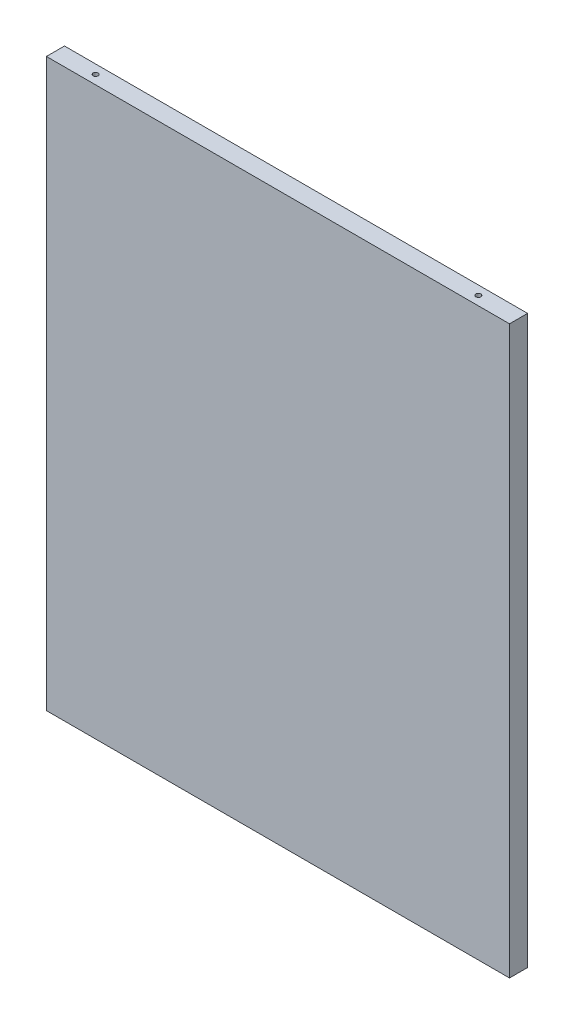
SolidWorks part; units mm, degrees
material "ДСП"
ref_plane "Спереди" through (0, 0, 0) normal (0, 0, 1) x (1, 0, 0)
ref_plane "Сверху" through (0, 0, 0) normal (0, 1, 0) x (1, 0, 0)
ref_plane "Справа" through (0, 0, 0) normal (1, 0, 0) x (0, 0, -1)
sketch "Эскиз1" plane through (0, 0, 0) normal (0, 0, 1) x (1, 0, 0)
  line L1 (0, 0) -> (461, 0)
  line L2 (0, 0) -> (0, 564)
  line L3 (0, 564) -> (461, 564)
  line L4 (461, 0) -> (461, 564)
  dimension "D1" = 564
  dimension "D2" = 461
extrude "Придание толщины" add sketch "Эскиз1" along normal blind 18
sketch "Эскиз3" plane through (0, 0, 18) normal (0, 0, 1) x (1, 0, 0)
  line L0 (0, 564) -> (0, 0) construction
  line L1 (0, 0) -> (461, 0) construction
  circle A0 centre (0, 0) radius 4
  dimension "D1" = 8
  dimension "D2" = 0
  dimension "D3" = 0
extrude "Отверстие 1" [suppressed] cut sketch "Эскиз3" against normal blind 16
sketch "Эскиз4" plane through (0, 0, 18) normal (0, 0, 1) x (1, 0, 0)
  line L0 (0, 564) -> (0, 0) construction
  line L1 (0, 0) -> (461, 0) construction
  circle A0 centre (0, 0) radius 4
  dimension "D2" = 0
  dimension "D3" = 8
extrude "Отверстие 2" [suppressed] cut sketch "Эскиз4" against normal blind 16
sketch "Эскиз5" plane through (0, 0, 18) normal (0, 0, 1) x (1, 0, 0)
  line L0 (0, 564) -> (0, 0) construction
  line L1 (0, 0) -> (461, 0) construction
  circle A0 centre (0, 0) radius 4
  dimension "D1" = 8
extrude "Отверстие 3" [suppressed] cut sketch "Эскиз5" against normal blind 16
sketch "Эскиз6" plane through (0, 0, 18) normal (0, 0, 1) x (1, 0, 0)
  line L0 (0, 564) -> (0, 0) construction
  line L1 (0, 0) -> (461, 0) construction
  circle A0 centre (0, 0) radius 4
  dimension "D1" = 8
extrude "Отверстие 4" [suppressed] cut sketch "Эскиз6" against normal blind 16
sketch "Эскиз7" plane through (0, 0, 18) normal (0, 0, 1) x (1, 0, 0)
  line L0 (0, 564) -> (0, 0) construction
  line L1 (0, 0) -> (461, 0) construction
  circle A0 centre (0, 0) radius 4
  dimension "D1" = 8
extrude "Отверстие 5" [suppressed] cut sketch "Эскиз7" against normal blind 16
sketch "Эскиз8" plane through (0, 0, 18) normal (0, 0, 1) x (1, 0, 0)
  line L0 (0, 564) -> (0, 0) construction
  line L1 (0, 0) -> (461, 0) construction
  circle A0 centre (0, 0) radius 4
  dimension "D1" = 8
extrude "Отверстие 6" [suppressed] cut sketch "Эскиз8" against normal blind 16
sketch "Эскиз9" plane through (0, 0, 18) normal (0, 0, 1) x (1, 0, 0)
  line L0 (0, 564) -> (0, 0) construction
  line L1 (0, 0) -> (461, 0) construction
  circle A0 centre (0, 0) radius 4
  dimension "D1" = 8
extrude "Отверстие 7" [suppressed] cut sketch "Эскиз9" against normal blind 16
sketch "Эскиз10" plane through (0, 0, 18) normal (0, 0, 1) x (1, 0, 0)
  line L0 (0, 564) -> (0, 0) construction
  line L1 (0, 0) -> (461, 0) construction
  circle A0 centre (0, 0) radius 4
  dimension "D1" = 8
extrude "Отверстие 8" [suppressed] cut sketch "Эскиз10" against normal blind 16
sketch "Эскиз27" plane through (0, 0, 18) normal (0, 0, 1) x (1, 0, 0)
  line L2 (0, 564) -> (0, 0) construction
  line L3 (0, 0) -> (461, 0) construction
  circle A0 centre (0, 0) radius 4
  dimension "D1" = 8
  dimension "D3" = 0
extrude "Отверстие 9" [suppressed] cut sketch "Эскиз27" against normal blind 10
sketch "Эскиз29" plane through (0, 0, 18) normal (0, 0, 1) x (1, 0, 0)
  line L2 (0, 564) -> (0, 0) construction
  line L3 (0, 0) -> (461, 0) construction
  circle A0 centre (0, 0) radius 4
  dimension "D1" = 8
extrude "Отверстие 10" [suppressed] cut sketch "Эскиз29" against normal blind 10
sketch "Эскиз30" plane through (0, 0, 18) normal (0, 0, 1) x (1, 0, 0)
  line L1 (0, 0) -> (461, 0) construction
  line L3 (0, 564) -> (0, 0) construction
  circle A0 centre (0, 0) radius 4
  dimension "D1" = 8
extrude "Отверстие 11" [suppressed] cut sketch "Эскиз30" against normal blind 10
sketch "Эскиз31" plane through (0, 0, 18) normal (0, 0, 1) x (1, 0, 0)
  line L2 (0, 0) -> (461, 0) construction
  line L3 (0, 564) -> (0, 0) construction
  circle A0 centre (0, 0) radius 4
  dimension "D1" = 8
extrude "Отверстие 12" [suppressed] cut sketch "Эскиз31" against normal blind 10
sketch "Эскиз11" plane through (0, 564, 0) normal (0, 1, 0) x (1, 0, 0)
  line L0 (0, -18) -> (0, 0) construction
  line L1 (461, -18) -> (0, -18) construction
  circle A0 centre (40, -9) radius 2.5
  dimension "D1" = 5
  dimension "D2" = 40
  dimension "D3" = 9
extrude "Отверстие А1" cut sketch "Эскиз11" against normal blind 37
sketch "Эскиз12" plane through (0, 564, 0) normal (0, 1, 0) x (1, 0, 0)
  line L1 (0, -18) -> (0, 0) construction
  line L2 (461, -18) -> (0, -18) construction
  circle A0 centre (421, -9) radius 2.5
  dimension "D1" = 5
  dimension "D3" = 9
  dimension "D2" = 421
extrude "Отверстие А2" cut sketch "Эскиз12" against normal blind 37
sketch "Эскиз13" plane through (0, 564, 0) normal (0, 1, 0) x (1, 0, 0)
  line L1 (0, -18) -> (0, 0) construction
  line L2 (461, -18) -> (0, -18) construction
  circle A0 centre (0, -18) radius 4
  dimension "D1" = 8
  dimension "D3" = 0
extrude "Отверстие А3" [suppressed] cut sketch "Эскиз13" against normal blind 20
sketch "Эскиз14" plane through (0, 564, 0) normal (0, 1, 0) x (1, 0, 0)
  line L0 (0, -18) -> (0, 0) construction
  line L1 (461, -18) -> (0, -18) construction
  circle A0 centre (0, -10) radius 4
  dimension "D1" = 8
  dimension "D3" = 8
extrude "Отверстие А4" [suppressed] cut sketch "Эскиз14" against normal blind 20
sketch "Эскиз15" plane through (461, 0, 0) normal (1, 0, 0) x (0, 0, -1)
  line L0 (-18, 564) -> (0, 564) construction
  line L1 (-18, 0) -> (-18, 564) construction
  circle A0 centre (-18, 564) radius 2.5
  dimension "D2" = 0
  dimension "D3" = 0
  dimension "D1" = 5
extrude "Отверстие В1" [suppressed] cut sketch "Эскиз15" against normal blind 37
sketch "Эскиз16" plane through (461, 0, 0) normal (1, 0, 0) x (0, 0, -1)
  line L0 (-18, 564) -> (0, 564) construction
  line L1 (-18, 0) -> (-18, 564) construction
  circle A0 centre (-18, 564) radius 2.5
  dimension "D1" = 5
extrude "Отверстие В2" [suppressed] cut sketch "Эскиз16" against normal blind 37
sketch "Эскиз17" plane through (461, 0, 0) normal (1, 0, 0) x (0, 0, -1)
  line L1 (-18, 564) -> (0, 564) construction
  line L2 (-18, 0) -> (-18, 564) construction
  circle A0 centre (-18, 564) radius 4
  dimension "D1" = 8
  dimension "D2" = 0
  dimension "D3" = 0
extrude "Отверстие В3" [suppressed] cut sketch "Эскиз17" against normal blind 20
sketch "Эскиз18" plane through (461, 0, 0) normal (1, 0, 0) x (0, 0, -1)
  line L0 (-18, 564) -> (0, 564) construction
  line L1 (-18, 0) -> (-18, 564) construction
  circle A0 centre (-18, 564) radius 4
  dimension "D3" = 0
  dimension "D1" = 0
  dimension "D2" = 8
extrude "Отверстие В4" [suppressed] cut sketch "Эскиз18" against normal blind 20
sketch "Эскиз19" plane through (0, 0, 0) normal (0, -1, 0) x (1, 0, 0)
  line L0 (461, 18) -> (461, 0) construction
  line L1 (0, 18) -> (461, 18) construction
  circle A0 centre (421, 9) radius 2.5
  dimension "D1" = 5
  dimension "D2" = 40
  dimension "D3" = 9
extrude "Отверстие С1" cut sketch "Эскиз19" against normal blind 37
sketch "Эскиз20" plane through (0, 0, 0) normal (0, -1, 0) x (1, 0, 0)
  line L0 (461, 18) -> (461, 0) construction
  line L1 (0, 18) -> (461, 18) construction
  circle A0 centre (40, 9) radius 2.5
  dimension "D3" = 9
  dimension "D2" = 5
  dimension "D1" = 421
extrude "Отверстие С2" cut sketch "Эскиз20" against normal blind 37
sketch "Эскиз21" plane through (0, 0, 0) normal (0, -1, 0) x (1, 0, 0)
  line L0 (461, 18) -> (461, 0) construction
  line L1 (0, 18) -> (461, 18) construction
  circle A0 centre (461, 18) radius 4
  dimension "D1" = 8
  dimension "D2" = 0
  dimension "D3" = 0
extrude "Отверстие С3" [suppressed] cut sketch "Эскиз21" against normal blind 20
sketch "Эскиз22" plane through (0, 0, 0) normal (0, -1, 0) x (1, 0, 0)
  line L0 (461, 18) -> (461, 0) construction
  line L1 (0, 18) -> (461, 18) construction
  circle A0 centre (461, 18) radius 4
  dimension "D1" = 8
  dimension "D2" = 0
  dimension "D3" = 0
extrude "Отверстие С4" [suppressed] cut sketch "Эскиз22" against normal blind 20
sketch "Эскиз23" plane through (0, 0, 0) normal (-1, 0, 0) x (0, 0, 1)
  line L0 (18, 0) -> (0, 0) construction
  line L1 (18, 564) -> (18, 0) construction
  circle A0 centre (18, 0) radius 2.5
  dimension "D2" = 0
  dimension "D3" = 0
  dimension "D1" = 5
extrude "Отверстие Д1" [suppressed] cut sketch "Эскиз23" against normal blind 37
sketch "Эскиз24" plane through (0, 0, 0) normal (-1, 0, 0) x (0, 0, 1)
  line L0 (18, 0) -> (0, 0) construction
  line L1 (18, 564) -> (18, 0) construction
  circle A0 centre (18, 0) radius 2.5
  dimension "D2" = 0
  dimension "D3" = 0
  dimension "D1" = 5
extrude "Отверстие Д2" [suppressed] cut sketch "Эскиз24" against normal blind 37
sketch "Эскиз25" plane through (0, 0, 0) normal (-1, 0, 0) x (0, 0, 1)
  line L0 (18, 0) -> (0, 0) construction
  line L1 (18, 564) -> (18, 0) construction
  circle A0 centre (18, 0) radius 4
  dimension "D1" = 8
  dimension "D2" = 0
  dimension "D3" = 0
extrude "Отверстие Д3" [suppressed] cut sketch "Эскиз25" against normal blind 20
sketch "Эскиз26" plane through (0, 0, 0) normal (-1, 0, 0) x (0, 0, 1)
  line L0 (18, 0) -> (0, 0) construction
  line L1 (18, 564) -> (18, 0) construction
  circle A0 centre (18, 0) radius 4
  dimension "D1" = 8
  dimension "D2" = 0
  dimension "D3" = 0
extrude "Отверстие Д4" [suppressed] cut sketch "Эскиз26" against normal blind 20
equation "\"D1@Придание толщины\" = \"Thick\""
equation "\"D2@Эскиз1\"=\"Width\""
equation "\"D1@Эскиз1\"=\"Height\""
equation "\"D1\" = 0"
equation "\"X1\" = 0"
equation "\"Y1\" = 0"
equation "\"H1\" = 0"
equation "\"D1@Эскиз3\"=\"D1\""
equation "\"D2@Эскиз3\"=\"X1\""
equation "\"D3@Эскиз3\"=\"Y1\""
equation "\"D1@Отверстие 1\"=\"H1\""
equation "\"D2\" = 0"
equation "\"X2\" = 0"
equation "\"Y2\" = 0"
equation "\"H2\" = 0"
equation "\"D3\" = 0"
equation "\"X3\" = 0"
equation "\"Y3\" = 0"
equation "\"H3\" = 0"
equation "\"D4\" = 0"
equation "\"X4\" = 0"
equation "\"Y4\" = 0"
equation "\"H4\" = 0"
equation "\"D5\" = 0"
equation "\"X5\" = 0"
equation "\"Y5\" = 0"
equation "\"H5\" = 0"
equation "\"D6\" = 0"
equation "\"X6\" = 0"
equation "\"Y6\" = 0"
equation "\"H6\" = 0"
equation "\"D7\" = 0"
equation "\"X7\" = 0"
equation "\"Y7\" = 0"
equation "\"H7\" = 0"
equation "\"D8\" = 0"
equation "\"X8\" = 0"
equation "\"Y8\" = 0"
equation "\"H8\" = 0"
equation "\"D3@Эскиз4\"=\"D2\""
equation "\"D1@Эскиз4\"=\"X2\""
equation "\"D2@Эскиз4\"=\"Y2\""
equation "\"D1@Отверстие 2\"=\"H2\""
equation "\"D2@Эскиз5\"=\"X3\""
equation "\"D1@Эскиз5\"=\"D3\""
equation "\"D3@Эскиз5\"=\"Y3\""
equation "\"D1@Отверстие 3\" = \"H3\""
equation "\"D1@Эскиз6\"=\"D4\""
equation "\"D2@Эскиз6\"=\"X4\""
equation "\"D3@Эскиз6\"=\"Y4\""
equation "\"D1@Отверстие 4\" = \"H4\""
equation "\"D1@Эскиз7\"=\"D5\""
equation "\"D2@Эскиз7\"=\"X5\""
equation "\"D3@Эскиз7\"=\"Y5\""
equation "\"D1@Отверстие 5\" = \"H5\""
equation "\"D1@Эскиз8\"=\"D6\""
equation "\"D2@Эскиз8\"=\"X6\""
equation "\"D3@Эскиз8\"=\"Y6\""
equation "\"D1@Отверстие 6\" = \"H6\""
equation "\"D1@Эскиз9\"=\"D7\""
equation "\"D2@Эскиз9\"=\"X7\""
equation "\"D3@Эскиз9\"=\"Y7\""
equation "\"D1@Отверстие 7\" = \"H7\""
equation "\"D1@Эскиз10\"=\"D8\""
equation "\"D2@Эскиз10\"=\"X8\""
equation "\"D3@Эскиз10\"=\"Y8\""
equation "\"D1@Отверстие 8\" = \"H8\""
equation "\"Отверстие 1\"= IIF ( \"D1\" = 0 , \"suppressed\" , \"unsuppressed\" )"
equation "\"Отверстие 2\"= IIF ( \"D2\" = 0 , \"suppressed\" , \"unsuppressed\" )"
equation "\"Отверстие 3\"= IIF ( \"D3\" = 0 , \"suppressed\" , \"unsuppressed\" )"
equation "\"Отверстие 4\"= IIF ( \"D4\" = 0 , \"suppressed\" , \"unsuppressed\" )"
equation "\"Отверстие 5\"= IIF ( \"D5\" = 0 , \"suppressed\" , \"unsuppressed\" )"
equation "\"Отверстие 6\" = IIF ( \"D6\" = 0 , \"suppressed\" , \"unsuppressed\" )"
equation "\"Отверстие 7\"= IIF ( \"D7\" = 0 , \"suppressed\" , \"unsuppressed\" )"
equation "\"Отверстие 8\"= IIF ( \"D8\" = 0 , \"suppressed\" , \"unsuppressed\" )"
equation "\"DA1\" = 5"
equation "\"XA1\" = 40"
equation "\"YA1\" = 9"
equation "\"HA1\" = 37"
equation "\"DA2\" = 5"
equation "\"XA2\" = 421"
equation "\"YA2\" = 9"
equation "\"HA2\" = 37"
equation "\"DA3\" = 0"
equation "\"XA3\" = 0"
equation "\"YA3\" = 0"
equation "\"DA4\" = 0"
equation "\"XA4\" = 0"
equation "\"YA4\" = 0"
equation "\"HA4\" = 0"
equation "\"D1@Эскиз11\"=\"DA1\""
equation "\"D2@Эскиз11\"=\"XA1\""
equation "\"D3@Эскиз11\"=\"YA1\""
equation "\"D1@Отверстие А1\" = \"HA1\""
equation "\"D1@Эскиз12\"=\"DA2\""
equation "\"D2@Эскиз12\"=\"XA2\""
equation "\"HA3\" = 0"
equation "\"D1@Эскиз13\"=\"DA3\""
equation "\"D2@Эскиз13\"=\"XA3\""
equation "\"D3@Эскиз13\"=\"YA3\""
equation "\"D1@Отверстие А3\" = \"HA3\""
equation "\"D1@Отверстие А2\" = \"HA2\""
equation "\"D1@Эскиз14\"=\"DA4\""
equation "\"D2@Эскиз14\"=\"XA4\""
equation "\"Отверстие А1\"= IIF ( \"DA1\" = 0 , \"suppressed\" , \"unsuppressed\" )"
equation "\"Отверстие А2\"= IIF ( \"DA2\" = 0 , \"suppressed\" , \"unsuppressed\" )"
equation "\"Отверстие А3\"= IIF ( \"DA3\" = 0 , \"suppressed\" , \"unsuppressed\" )"
equation "\"Отверстие А4\"= IIF ( \"DA4\" = 0 , \"suppressed\" , \"unsuppressed\" )"
equation "\"DB1\" = 0"
equation "\"XB1\" = 0"
equation "\"YB1\" = 0"
equation "\"HB1\" = 0"
equation "\"DB2\" = 0"
equation "\"XB2\" = 0"
equation "\"YB2\" = 0"
equation "\"HB2\" = 0"
equation "\"DB3\" = 0"
equation "\"XB3\" = 0"
equation "\"YB3\" = 0"
equation "\"HB3\" = 0"
equation "\"DB4\" = 0"
equation "\"XB4\" = 0"
equation "\"YB4\" = 0"
equation "\"HB4\" = 0"
equation "\"DC1\" = 5"
equation "\"XC1\" = 40"
equation "\"YC1\" = 9"
equation "\"HC1\" = 37"
equation "\"DC2\" = 5"
equation "\"XC2\" = 421"
equation "\"YC2\" = 9"
equation "\"HC2\" = 37"
equation "\"DC3\" = 0"
equation "\"XC3\" = 0"
equation "\"YC3\" = 0"
equation "\"HC3\" = 0"
equation "\"DC4\" = 0"
equation "\"XC4\" = 0"
equation "\"YC4\" = 0"
equation "\"HC4\" = 0"
equation "\"DD1\" = 0"
equation "\"XD1\" = 0"
equation "\"YD1\" = 0"
equation "\"HD1\" = 0"
equation "\"DD2\" = 0"
equation "\"XD2\" = 0"
equation "\"YD2\" = 0"
equation "\"HD2\" = 0"
equation "\"DD3\" = 0"
equation "\"XD3\" = 0"
equation "\"YD3\" = 0"
equation "\"HD3\" = 0"
equation "\"DD4\" = 0"
equation "\"XD4\" = 0"
equation "\"YD4\" = 0"
equation "\"HD4\" = 0"
equation "\"D1@Эскиз15\"=\"DB1\""
equation "\"D2@Эскиз15\"=\"XB1\""
equation "\"D3@Эскиз15\"=\"YB1\""
equation "\"D1@Отверстие В1\" = \"HB1\""
equation "\"D1@Эскиз16\"=\"DB2\""
equation "\"D2@Эскиз16\"=\"XB2\""
equation "\"D3@Эскиз16\"=\"YB2\""
equation "\"D1@Отверстие В2\" = \"HB2\""
equation "\"D1@Эскиз17\"=\"DB3\""
equation "\"D2@Эскиз17\"=\"XB3\""
equation "\"D3@Эскиз17\"=\"YB3\""
equation "\"D1@Отверстие В3\" = \"HB3\""
equation "\"D1@Эскиз18\"=\"XB4\""
equation "\"D2@Эскиз18\"=\"DB4\""
equation "\"D3@Эскиз18\"=\"YB4\""
equation "\"D1@Отверстие В4\" = \"HB4\""
equation "\"D1@Эскиз19\"=\"DC1\""
equation "\"D2@Эскиз19\"=\"XC1\""
equation "\"D3@Эскиз19\"=\"YC1\""
equation "\"D1@Отверстие С1\" = \"HC1\""
equation "\"D1@Эскиз20\"=\"XC2\""
equation "\"D2@Эскиз20\"=\"DC2\""
equation "\"D3@Эскиз20\"=\"YC2\""
equation "\"D1@Отверстие С2\" = \"HC2\""
equation "\"D1@Эскиз21\"=\"DC3\""
equation "\"D2@Эскиз21\"=\"XC3\""
equation "\"D3@Эскиз21\"=\"YC3\""
equation "\"D1@Отверстие С3\" = \"HC3\""
equation "\"D1@Эскиз22\"=\"DC4\""
equation "\"D2@Эскиз22\"=\"XC4\""
equation "\"D3@Эскиз22\"=\"YC4\""
equation "\"D1@Отверстие С4\" = \"HC4\""
equation "\"D1@Эскиз23\"=\"DD1\""
equation "\"D2@Эскиз23\"=\"XD1\""
equation "\"D3@Эскиз23\"=\"YD1\""
equation "\"D1@Отверстие Д1\" = \"HD1\""
equation "\"D1@Эскиз24\"=\"DD2\""
equation "\"D2@Эскиз24\"=\"XD2\""
equation "\"D3@Эскиз24\"=\"YD2\""
equation "\"D1@Отверстие Д2\" = \"HD2\""
equation "\"D1@Эскиз25\"=\"DD3\""
equation "\"D2@Эскиз25\"=\"XD3\""
equation "\"D3@Эскиз25\"=\"YD3\""
equation "\"D1@Отверстие Д3\" = \"HD3\""
equation "\"D1@Эскиз26\"=\"DD4\""
equation "\"D2@Эскиз26\"=\"XD4\""
equation "\"D3@Эскиз26\"=\"YD4\""
equation "\"D1@Отверстие Д4\" = \"HD4\""
equation "\"Отверстие В1\"= IIF ( \"DB1\" = 0 , \"suppressed\" , \"unsuppressed\" )"
equation "\"Отверстие В2\"= IIF ( \"DB2\" = 0 , \"suppressed\" , \"unsuppressed\" )"
equation "\"Отверстие В3\"= IIF ( \"DB3\" = 0 , \"suppressed\" , \"unsuppressed\" )"
equation "\"Отверстие В4\"= IIF ( \"DB4\" = 0 , \"suppressed\" , \"unsuppressed\" )"
equation "\"Отверстие С1\"= IIF ( \"DC1\" = 0 , \"suppressed\" , \"unsuppressed\" )"
equation "\"Отверстие С2\"= IIF ( \"DC2\" = 0 , \"suppressed\" , \"unsuppressed\" )"
equation "\"Отверстие С3\"= IIF ( \"DC3\" = 0 , \"suppressed\" , \"unsuppressed\" )"
equation "\"Отверстие С4\"= IIF ( \"DC4\" = 0 , \"suppressed\" , \"unsuppressed\" )"
equation "\"Отверстие Д1\"= IIF ( \"DD1\" = 0 , \"suppressed\" , \"unsuppressed\" )"
equation "\"Отверстие Д2\"= IIF ( \"DD2\" = 0 , \"suppressed\" , \"unsuppressed\" )"
equation "\"Отверстие Д3\"= IIF ( \"DD3\" = 0 , \"suppressed\" , \"unsuppressed\" )"
equation "\"Отверстие Д4\"= IIF ( \"DD4\" = 0 , \"suppressed\" , \"unsuppressed\" )"
equation "\"D9\" = 0"
equation "\"X9\" = 0"
equation "\"Y9\" = 0"
equation "\"H9\" = 0"
equation "\"D10\" = 0"
equation "\"X10\" = 0"
equation "\"Y10\" = 0"
equation "\"H10\" = 0"
equation "\"D11\" = 0"
equation "\"X11\" = 0"
equation "\"Y11\" = 0"
equation "\"H11\" = 0"
equation "\"D12\" = 0"
equation "\"X12\" = 0"
equation "\"Y12\" = 0"
equation "\"H12\" = 0"
equation "\"D1@Эскиз27\"=\"D9\""
equation "\"D2@Эскиз27\"=\"X9\""
equation "\"D3@Эскиз27\"=\"Y9\""
equation "\"D1@Отверстие 9\" = \"H9\""
equation "\"D1@Эскиз29\"=\"D10\""
equation "\"D2@Эскиз29\"=\"X10\""
equation "\"D3@Эскиз29\"=\"Y10\""
equation "\"D1@Отверстие 10\" = \"H10\""
equation "\"D1@Эскиз30\"=\"D11\""
equation "\"D2@Эскиз30\"=\"X11\""
equation "\"D3@Эскиз30\"=\"Y11\""
equation "\"D1@Отверстие 11\" = \"H11\""
equation "\"D1@Эскиз31\"=\"D12\""
equation "\"D2@Эскиз31\"=\"X12\""
equation "\"D3@Эскиз31\"=\"Y12\""
equation "\"D1@Отверстие 12\" = \"H12\""
equation "\"Отверстие 9\"= IIF ( \"D9\" = 0 , \"suppressed\" , \"unsuppressed\" )"
equation "\"Отверстие 10\"= IIF ( \"D10\" = 0 , \"suppressed\" , \"unsuppressed\" )"
equation "\"Отверстие 11\"= IIF ( \"D11\" = 0 , \"suppressed\" , \"unsuppressed\" )"
equation "\"Отверстие 12\"= IIF ( \"D12\" = 0 , \"suppressed\" , \"unsuppressed\" )"
equation "\"Height\" = 564"
equation "\"Width\" = 461"
equation "\"Thick\" = 18"
equation "\"D3@Эскиз12\"=\"YA2\""
